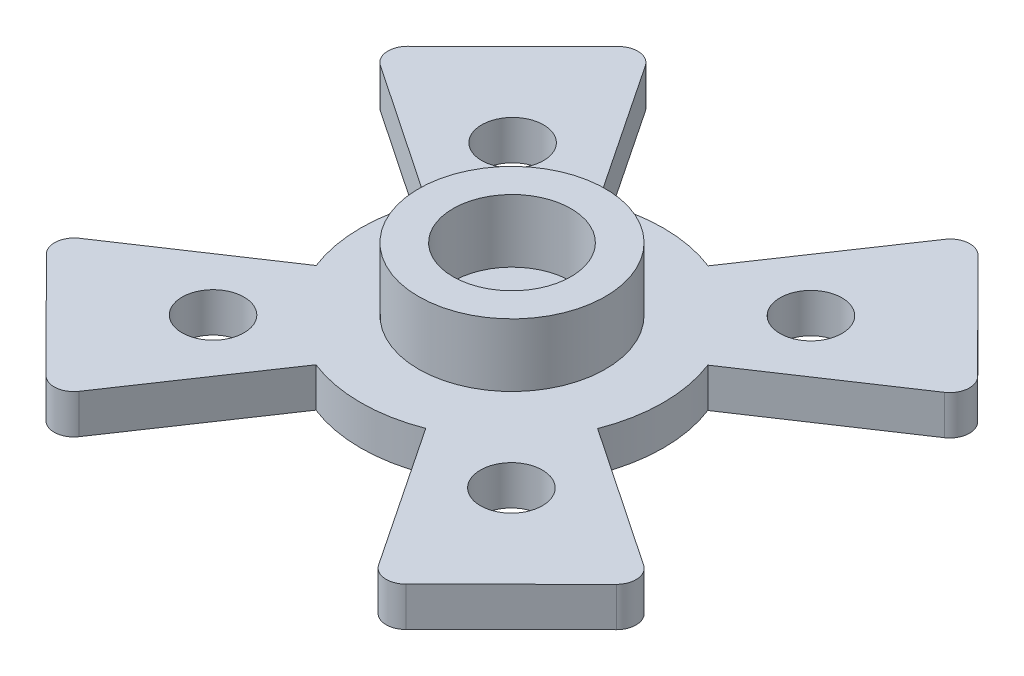
SolidWorks part; units mm, degrees
ref_plane "Front Plane" through (0, 0, 0) normal (0, 0, 1) x (1, 0, 0)
ref_plane "Top Plane" through (0, 0, 0) normal (0, 1, 0) x (1, 0, 0)
ref_plane "Right Plane" through (0, 0, 0) normal (1, 0, 0) x (0, 0, -1)
sketch "Sketch1" plane through (0, 0, 0) normal (0, 1, 0) x (1, 0, 0)
  line L0 (-3, 0) -> (3, 0)
  line L1 (0, 3) -> (0, -3)
  line L2 (0, 3) -> (8.3396, 15.362)
  line L3 (8.3396, 15.362) -> (15.3971, 8.2773)
  line L4 (15.3971, 8.2773) -> (3, 0)
  line L5 (11.8684, 11.8197) -> (3.3657, 3.3518)
  line L6 (15.362, -8.3396) -> (8.2773, -15.3971)
  line L7 (3, 0) -> (15.362, -8.3396)
  line L8 (8.2773, -15.3971) -> (0, -3)
  line L9 (-8.3396, -15.362) -> (-15.3971, -8.2773)
  line L10 (0, -3) -> (-8.3396, -15.362)
  line L11 (-15.3971, -8.2773) -> (-3, 0)
  line L12 (-15.362, 8.3396) -> (-8.2773, 15.3971)
  line L13 (-3, 0) -> (-15.362, 8.3396)
  line L14 (-8.2773, 15.3971) -> (0, 3)
  circle A0 centre (0, 0) radius 3
  circle A1 centre (0, 0) radius 4.75
  circle A3 centre (7.617, 7.5857) radius 1.575
  circle A4 centre (7.5857, -7.617) radius 1.575
  circle A5 centre (-7.617, -7.5857) radius 1.575
  circle A6 centre (-7.5857, 7.617) radius 1.575
  circle A7 centre (0, 0) radius 7.6944
  point P35 (0, 0)
  dimension "D1" = 6
  dimension "D3" = 9.5
  dimension "D5" = 4
  dimension "D4" = 3.15
  dimension "D2" = 10
  dimension "D6" = 12
extrude "Boss-Extrude1" add sketch "Sketch1" along normal blind 2 contours A1 L11 L9 L10 A5 | A1 L8 L6 L7 A4 | A3 L5 A1 L4 L3 | A3 L5 L3 L2 A1 | A1 L14 L12 L13 A6 | L1 A0 L0 | L0 A0 L1 | L1 A0 L0 | L0 A0 L1 | L4 A7 L5 A1 | L5 A7 L2 A1 | L7 A7 L4 A1 | L8 A7 L7 A1 | L10 A7 L8 A1 | L11 A7 L10 A1 | L13 A7 L11 A1 | L14 A7 L13 A1 | L2 A7 L14 A1 region at (-1.2732, 0, -1.2732) region at (-1.2732, 0, 1.2732) region at (1.2732, 0, -1.2732) region at (1.2732, 0, 1.2732) region at (-4.2799, 0, 4.2679) region at (-6.3238, 0, -0.009) region at (-4.2679, 0, -4.2799) region at (-8.9635, 0, 8.9293) region at (-0.009, 0, 6.3238) region at (-8.9293, 0, -8.9635) region at (0.009, 0, -6.3238) region at (3.2722, 0, -5.2787) region at (4.2679, 0, 4.2799) region at (5.2905, 0, -3.2543) region at (6.3238, 0, 0.009) region at (7.372, 0, -10.5254) region at (8.9293, 0, 8.9635) region at (10.5565, 0, -7.3316)
extrude "Boss-Extrude2" add sketch "Sketch1<3>" along normal blind 5.2 contours L14 A1 L13 A0 | L2 A1 L14 | L4 A1 L2 A0 | L7 A1 L4 | L8 A1 L7 A0 | L10 A1 L8 | L11 A1 L10 A0 | L13 A1 L11 region at (-2.5681, 0, 2.5645) region at (-4.1381, 0, -0.0034) region at (-2.5645, 0, -2.5681) region at (0.0034, 0, -4.1381) region at (2.5681, 0, -2.5645) region at (2.5645, 0, 2.5681) region at (-0.0034, 0, 4.1381) region at (4.1381, 0, 0.0034)
sketch "Sketch1<3>" plane through (0, 0, 0) normal (0, 1, 0) x (1, 0, 0) same geometry as "Sketch1"
fillet "Fillet1" radius 1 8 edges at (-15.362, 1, -8.3396) (-8.2773, 1, -15.3971) (8.3396, 1, -15.362) (15.362, 1, 8.3396) (15.3971, 1, -8.2773) (8.2773, 1, 15.3971) (-15.3971, 1, 8.2773) (-8.3396, 1, 15.362)
